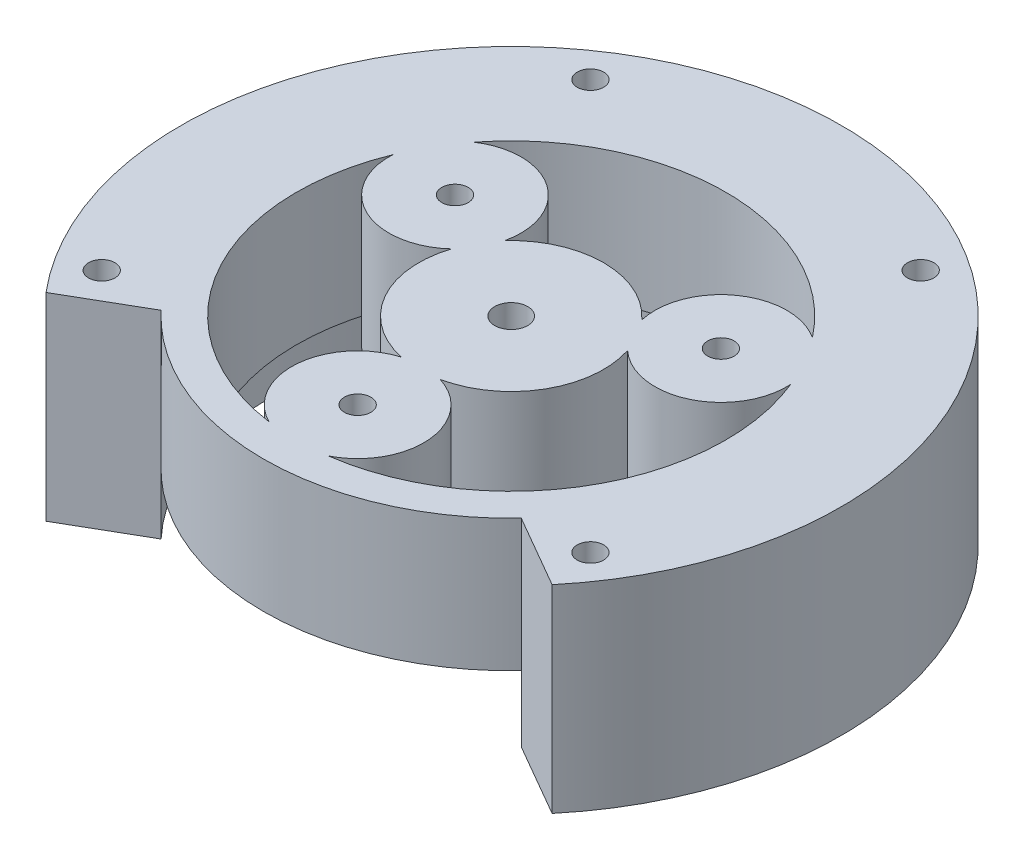
SolidWorks part; units mm, degrees
ref_plane "前视基准面" through (0, 0, 0) normal (0, 0, 1) x (1, 0, 0)
ref_plane "上视基准面" through (0, 0, 0) normal (0, 1, 0) x (1, 0, 0)
ref_plane "右视基准面" through (0, 0, 0) normal (1, 0, 0) x (0, 0, -1)
ref_plane "基准面4" through (0, -20, 0) normal (0, -1, 0) x (1, 0, 0)
sketch "草图1" plane through (0, -20, 0) normal (0, -1, 0) x (1, 0, 0)
  line L0 (-27.2679, 25.7431) -> (-38.3167, 32.1221)
  line L1 (38.3167, 32.1221) -> (27.2679, 25.7431)
  arc A0 (27.2679, 25.7431) -> (-27.2679, 25.7431) centre (0, 0) ccw
  arc A1 (-38.3167, 32.1221) -> (38.3167, 32.1221) centre (0, 0) ccw
extrude "凸台-拉伸1" add sketch "草图1" against normal blind 20
sketch "草图2" plane through (0, -20, 0) normal (0, -1, 0) x (1, 0, 0)
  line L0 (27.2679, 25.7431) -> (38.3167, 32.1221)
  line L1 (-38.3167, 32.1221) -> (-27.2679, 25.7431)
  arc A0 (38.3167, 32.1221) -> (-38.3167, 32.1221) centre (0, 0) cw
  arc A1 (-27.2679, 25.7431) -> (27.2679, 25.7431) centre (0, 0) ccw
extrude "凸台-拉伸2" add sketch "草图2" along normal blind 10
sketch "草图3" plane through (0, -20, 0) normal (0, -1, 0) x (1, 0, 0)
  arc A0 (4.4816, 32.1895) -> (2.9321, 13.6895) centre (0, 23.25) cw
  arc A1 (2.9321, 13.6895) -> (13.3215, -4.3055) centre (0, 0) cw
  arc A2 (13.3215, -4.3055) -> (30.1178, -12.2135) centre (20.1351, -11.625) cw
  arc A3 (30.1178, -12.2135) -> (4.4816, 32.1895) centre (0, 0) ccw
extrude "切除-拉伸1" cut sketch "草图3" against normal through all
sketch "草图4" plane through (0, -20, 0) normal (0, -1, 0) x (1, 0, 0)
  arc A0 (-13.3215, -4.3055) -> (-2.9321, 13.6895) centre (0, 0) cw
  arc A1 (-2.9321, 13.6895) -> (-4.4816, 32.1895) centre (0, 23.25) cw
  arc A2 (-4.4816, 32.1895) -> (-30.1178, -12.2135) centre (0, 0) ccw
  arc A3 (-30.1178, -12.2135) -> (-13.3215, -4.3055) centre (-20.1351, -11.625) cw
extrude "切除-拉伸2" cut sketch "草图4" against normal through all
sketch "草图5" plane through (0, 0, 0) normal (0, 1, 0) x (-1, 0, 0)
  arc A0 (-25.6361, -19.976) -> (25.6361, -19.976) centre (0, 0) ccw
  arc A1 (25.6361, -19.976) -> (10.3894, -9.384) centre (20.1351, -11.625) cw
  arc A2 (10.3894, -9.384) -> (-10.3894, -9.384) centre (0, 0) cw
  arc A3 (-10.3894, -9.384) -> (-25.6361, -19.976) centre (-20.1351, -11.625) cw
extrude "切除-拉伸3" cut sketch "草图5" against normal through all
sketch "草图6" plane through (0, -20, 0) normal (0, -1, 0) x (1, 0, 0)
  line L0 (-8, -9.5) -> (-8, 9.5)
  line L1 (-8, 9.5) -> (-1, 9.5)
  line L2 (-1, 9.5) -> (-1, -9.5)
  line L3 (-1, -9.5) -> (-8, -9.5)
extrude "凸台-拉伸3" add sketch "草图6" along normal blind 9
sketch "草图7" plane through (0, -20, 0) normal (0, -1, 0) x (1, 0, 0)
  line L0 (1, 9.5) -> (8, 9.5)
  line L1 (8, 9.5) -> (8, -9.5)
  line L2 (8, -9.5) -> (1, -9.5)
  line L3 (1, -9.5) -> (1, 9.5)
extrude "凸台-拉伸4" add sketch "草图7" along normal blind 9
hole_wizard "Ø4.0 (4) 直径孔1" positions "草图9" profile "草图8" hole size "Ø4.0" standard "ANSI Metric"
sketch "草图9" plane through (0, 0, 0) normal (0, 1, 0) x (1, 0, 0)
  point P0 (-37, -25)
  point P1 (-25, 37)
  point P2 (37, -25)
  point P3 (25, 37)
sketch "草图8" plane through (-37, 0, 25) normal (1, 0, 0) x (0, 0, 1)
  line L0 (0, 0) -> (0, 30)
  line L1 (0, 30) -> (2, 30)
  line L2 (2, 30) -> (2, 0)
  line L5 (2, 0) -> (0, 0)
  line L11 (0, -6.35) -> (0, 107.95) construction
  dimension "通孔孔直径" = 4
  dimension "通孔孔深度" = 30
hole_wizard "Ø5.0 (5) 直径孔1" positions "草图11" profile "草图10" hole size "Ø5.0" standard "ANSI Metric"
sketch "草图11" plane through (0, 0, 0) normal (0, 1, 0) x (1, 0, 0)
  point P0 (0, 0)
sketch "草图10" plane through (0, 0, 0) normal (1, 0, 0) x (0, 0, 1)
  line L0 (0, 0) -> (0, 30)
  line L1 (0, 30) -> (2.5, 30)
  line L2 (2.5, 30) -> (2.5, 0)
  line L5 (2.5, 0) -> (0, 0)
  line L11 (0, -6.35) -> (0, 107.95) construction
  dimension "通孔孔直径" = 5
  dimension "通孔孔深度" = 30
hole_wizard "Ø4.0 (4) 直径孔2" positions "草图13" profile "草图12" hole size "Ø4.0" standard "ANSI Metric"
sketch "草图13" plane through (0, 0, 0) normal (0, 1, 0) x (1, 0, 0)
  point P0 (-20.1351, 11.625)
  point P1 (0, -23.25)
  point P2 (20.1351, 11.625)
sketch "草图12" plane through (-20.1351, 0, -11.625) normal (1, 0, 0) x (0, 0, 1)
  line L0 (0, 0) -> (0, 30)
  line L1 (0, 30) -> (2, 30)
  line L2 (2, 30) -> (2, 0)
  line L5 (2, 0) -> (0, 0)
  line L11 (0, -6.35) -> (0, 107.95) construction
  dimension "通孔孔直径" = 4
  dimension "通孔孔深度" = 30
